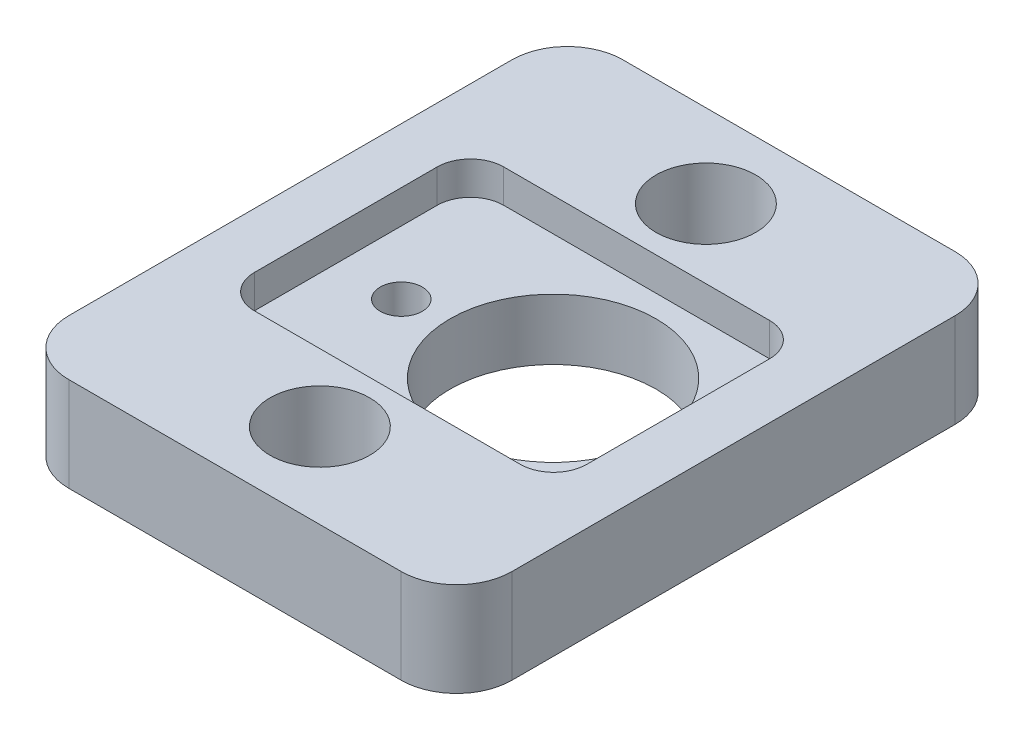
SolidWorks part; units mm, degrees
ref_plane "Front Plane" through (0, 0, 0) normal (0, 0, 1) x (1, 0, 0)
ref_plane "Top Plane" through (0, 0, 0) normal (0, 1, 0) x (1, 0, 0)
ref_plane "Right Plane" through (0, 0, 0) normal (1, 0, 0) x (0, 0, -1)
sketch "Sketch1" plane through (0, 0, 0) normal (0, 1, 0) x (1, 0, 0)
  line L1 (2, 0) -> (14, 0)
  line L2 (0, -2) -> (0, -18)
  line L3 (2, -20) -> (14, -20)
  line L4 (16, -2) -> (16, -18)
  arc A0 (0, -18) -> (2, -20) centre (2, -18) ccw
  arc A1 (14, -20) -> (16, -18) centre (14, -18) ccw
  arc A2 (14, 0) -> (16, -2) centre (14, -2) cw
  arc A3 (2, 0) -> (0, -2) centre (2, -2) ccw
  point P7 (0, -20)
  point P12 (16, 0)
  point P15 (0, 0)
  dimension "D3" = 2
  dimension "D1" = 16
  dimension "D2" = 20
extrude "Boss-Extrude1" add sketch "Sketch1" along normal blind 3.4
sketch "Sketch2" plane through (0, 3.4, 0) normal (0, 1, 0) x (1, 0, 0)
  line L0 (14, 0) -> (2, 0) construction
  line L1 (3.2, -5.5) -> (12.8, -5.5)
  line L2 (2, -6.7) -> (2, -13.3)
  line L3 (3.2, -14.5) -> (12.8, -14.5)
  line L4 (14, -6.7) -> (14, -13.3)
  line L5 (16, -18) -> (16, -2) construction
  arc A0 (2, -13.3) -> (3.2, -14.5) centre (3.2, -13.3) ccw
  arc A1 (12.8, -14.5) -> (14, -13.3) centre (12.8, -13.3) ccw
  arc A2 (12.8, -5.5) -> (14, -6.7) centre (12.8, -6.7) cw
  arc A3 (3.2, -5.5) -> (2, -6.7) centre (3.2, -6.7) ccw
  point P4 (8, -5.5)
  point P9 (2, -14.5)
  point P14 (14, -5.5)
  point P17 (2, -5.5)
  dimension "D4" = 1.2
  dimension "D1" = 12
  dimension "D2" = 9
  dimension "D3" = 5.5
  dimension "D5" = 2
extrude "Cut-Extrude1" cut sketch "Sketch2" against normal blind 1.2
sketch "Sketch3" plane through (0, 2.2, 0) normal (0, 1, 0) x (1, 0, 0)
  line L0 (14, -13.3) -> (14, -6.7) construction
  circle A0 centre (9.5, -10.0174) radius 3.72
  dimension "D1" = 7.44
  dimension "D2" = 4.5
extrude "Cut-Extrude2" cut sketch "Sketch3" against normal through all
sketch "Sketch4" plane through (0, 3.4, 0) normal (0, 1, 0) x (1, 0, 0)
  line L1 (0, -2) -> (0, -18) construction
  line L2 (14, 0) -> (2, 0) construction
  circle A0 centre (8, -3) radius 1.8
  circle A2 centre (8, -16.9366) radius 1.8
  dimension "D1" = 3
  dimension "D2" = 8
extrude "Cut-Extrude3" cut sketch "Sketch4" against normal through all
sketch "Sketch5" plane through (0, 2.2, 0) normal (0, 1, 0) x (1, 0, 0)
  circle A0 centre (4.2868, -10.2839) radius 0.76
  circle A1 centre (9.5, -10.0174) radius 3.72 construction
  dimension "D1" = 1.5
  dimension "D2" = 1.52
extrude "Cut-Extrude4" cut sketch "Sketch5" against normal blind 10
